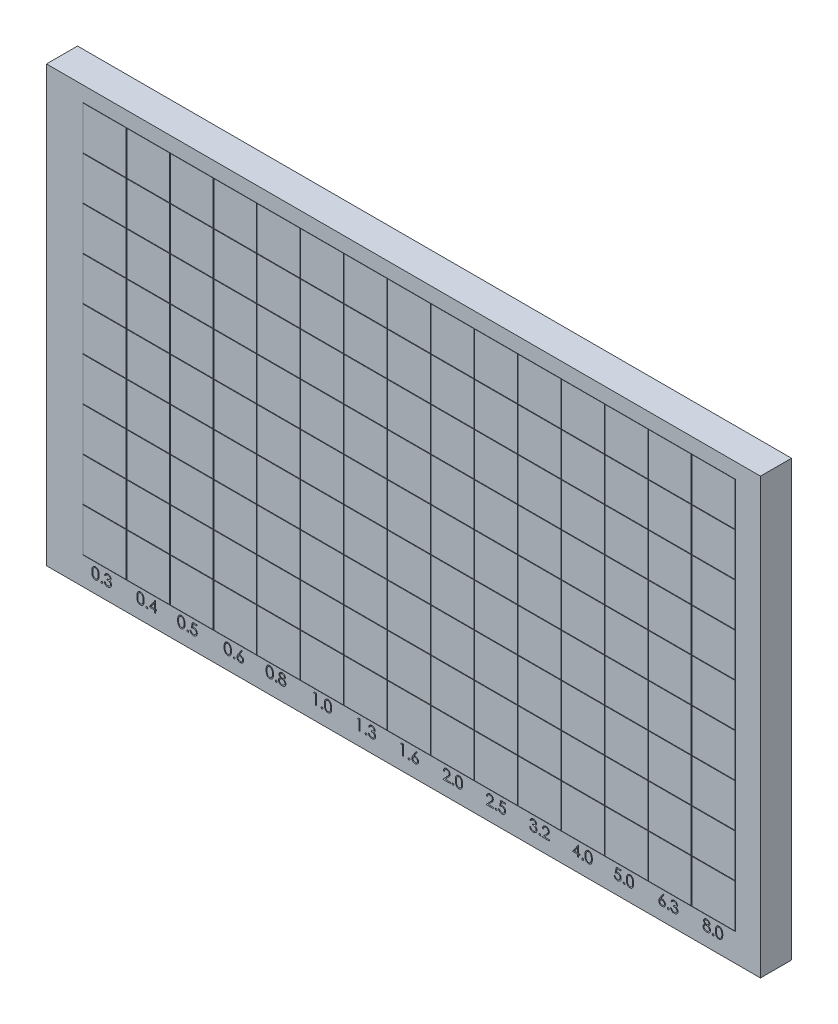
SolidWorks part; units mm, degrees
ref_plane "Front Plane" through (0, 0, 0) normal (0, 0, 1) x (1, 0, 0)
ref_plane "Top Plane" through (0, 0, 0) normal (0, 1, 0) x (1, 0, 0)
ref_plane "Right Plane" through (0, 0, 0) normal (1, 0, 0) x (0, 0, -1)
sketch "Sketch1" plane through (0, 0, 0) normal (0, 0, 1) x (1, 0, 0)
  line L1 (-115, -70) -> (115, -70)
  line L2 (-115, -70) -> (-115, 70)
  line L3 (-115, 70) -> (115, 70)
  line L4 (115, -70) -> (115, 70)
  line L5 (-115, -70) -> (115, 70) construction
  line L6 (-115, 70) -> (115, -70) construction
  point P0 (0, 0)
extrude "Boss-Extrude1" add sketch "Sketch1" along normal blind 10
sketch "Sketch4" plane through (0, 0, 10) normal (0, 0, 1) x (1, 0, 0)
  line L24 (-103.3067, 65.1) -> (-103.3067, 50.9)
  line L25 (-103.2067, 65) -> (-89.2067, 65)
  line L26 (-103.2067, 65) -> (-103.2067, 51)
  line L27 (-103.2067, 51) -> (-89.2067, 51)
  line L28 (-89.2067, 65) -> (-89.2067, 51)
  line L29 (-103.3067, 50.9) -> (-89.1067, 50.9)
  line L30 (-89.1067, 65.1) -> (-89.1067, 50.9)
  line L31 (-103.3067, 65.1) -> (-89.1067, 65.1)
  line L32 (115, 70) -> (-115, 70) construction
  dimension "D1" = 0.1
  dimension "D2" = 14
  dimension "D3" = 14
  dimension "D4" = 5
extrude "Cut-Extrude2" cut sketch "Sketch4" against normal blind 8
pattern_linear "LPattern2" count 15 spacing 14 along (1, 0, 0) count 9 spacing 14 along (0, -1, 0) of "Cut-Extrude2"
sketch "Sketch5" plane through (0, 0, 10) normal (0, 0, 1) x (1, 0, 0)
  text T0 "0.3"
  text T2 "0.4"
  text T3 "0.5\r\n"
  text T4 "0.6\r\n"
  text T5 "0.8"
  text T6 "1.0\r\n"
  text T7 "1.3\r\n"
  text T8 "1.6"
  text T9 "2.0"
  text T10 "2.5\r\n"
  text T11 "3.2\r\n"
  text T12 "4.0"
  text T13 "5.0"
  text T14 "6.3"
  text T15 "8.0"
  point P16 (-100.54, -65.9628)
  point P18 (0, 0)
extrude "Cut-Extrude3" cut sketch "Sketch5" against normal blind 2
